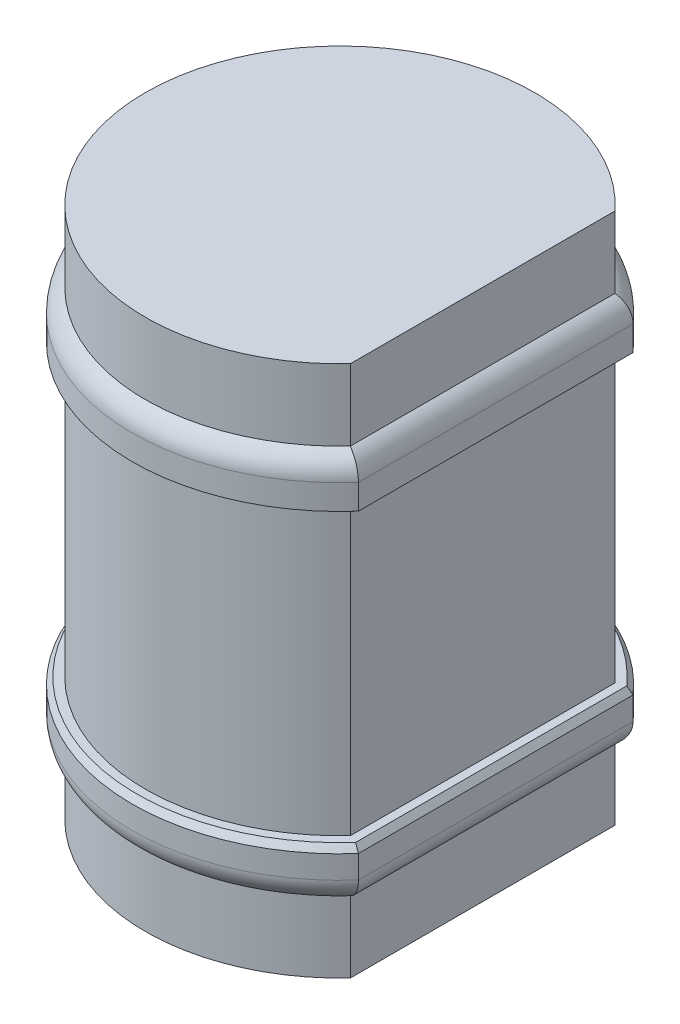
SolidWorks part; units mm, degrees
ref_plane "Front Plane" through (0, 0, 0) normal (0, 0, 1) x (1, 0, 0)
ref_plane "Top Plane" through (0, 0, 0) normal (0, 1, 0) x (1, 0, 0)
ref_plane "Right Plane" through (0, 0, 0) normal (1, 0, 0) x (0, 0, -1)
sketch "Sketch1" plane through (0, 0, 0) normal (0, 1, 0) x (1, 0, 0)
  line L0 (7.5, 0) -> (5.5, 0) construction
  line L1 (5.5, 5.099) -> (5.5, -5.099)
  line L3 (5.5, 0) -> (0, 0) construction
  arc A1 (5.5, 5.099) -> (5.5, -5.099) centre (0, 0) ccw
extrude "Boss-Extrude1" add sketch "Sketch1" along normal mid plane 20.5 contours L1 A1
ref_plane "SnapFeature-Plane1" through (0, 6.5, 0) normal (0, 1, 0) x (1, 0, 0)
ref_plane "SnapeFeature-Plane2" through (0, -6.5, 0) normal (0, 1, 0) x (1, 0, 0)
sketch "Sketch2" plane through (0, 6.5, 0) normal (0, 1, 0) x (1, 0, 0)
  line L0 (5.5, 0) -> (6, 0) construction
  line L1 (5.5, 5.099) -> (5.5, -5.099) construction
  line L2 (6, 5.2915) -> (6, -5.2915)
  arc A1 (6, 5.2915) -> (6, -5.2915) centre (0, 0) ccw
extrude "Boss-Extrude2" add sketch "Sketch2" along normal mid plane 2
sketch "Sketch3" plane through (0, -6.5, 0) normal (0, 1, 0) x (1, 0, 0)
  line L0 (6, -5.2915) -> (6, 5.2915) construction
  line L1 (6, -5.2915) -> (6, 5.2915)
  arc A0 (6, 5.2915) -> (6, -5.2915) centre (0, 0) ccw
extrude "Boss-Extrude3" add sketch "Sketch3" along normal mid plane 2 contours L1 A0
fillet "Fillet1" radius 1 4 edges at (6, 7.5, 0) (-8, 7.5, 0) (6, -7.5, 0) (-8, -7.5, 0)
chamfer "Chamfer1" distance 0.25 angle 35 4 edges at (6, 5.5, 0) (-8, 5.5, 0) (6, -5.5, 0) (-8, -5.5, 0) first distance on face at (-1, 5.5, 0) first distance on face at (6, -6.067, 0) first distance on face at (-1, -6.067, 0)
